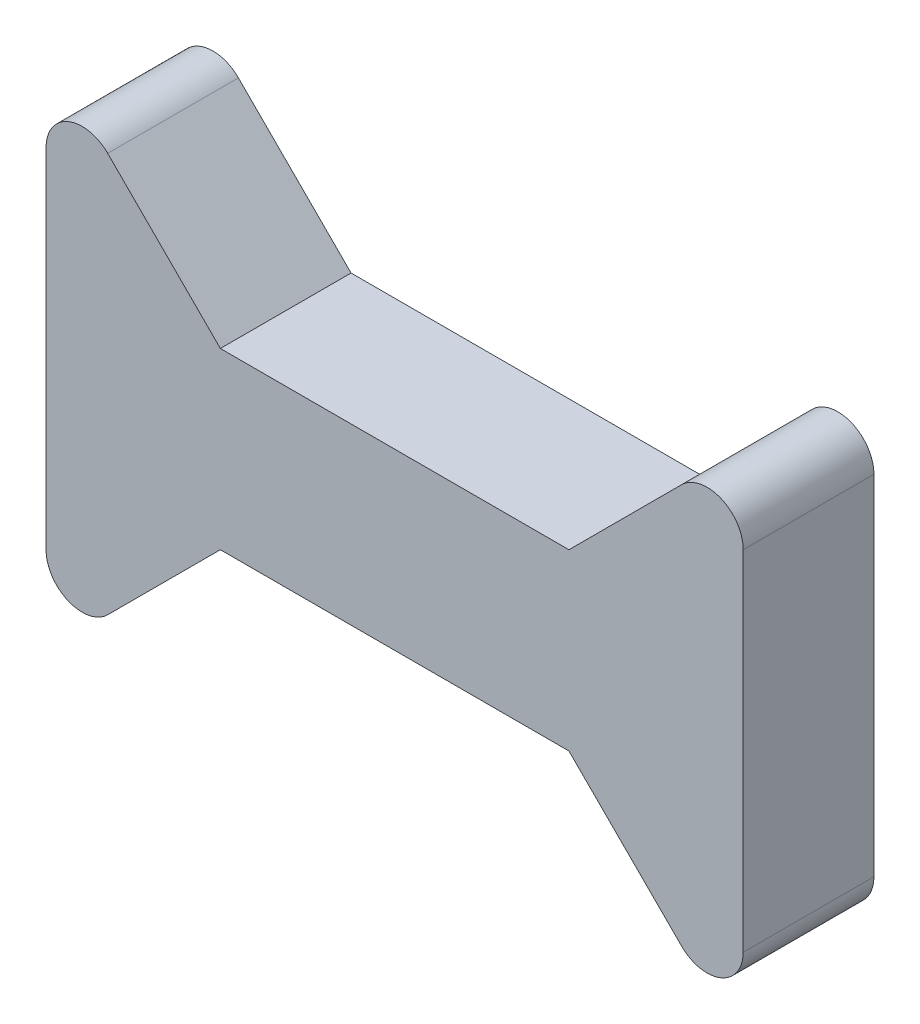
SolidWorks part; units mm, degrees
ref_plane "Front Plane" through (0, 0, 0) normal (0, 0, 1) x (1, 0, 0)
ref_plane "Top Plane" through (0, 0, 0) normal (0, 1, 0) x (1, 0, 0)
ref_plane "Right Plane" through (0, 0, 0) normal (1, 0, 0) x (0, 0, -1)
sketch "Sketch1" plane through (0, 0, 0) normal (0, 0, 1) x (1, 0, 0)
  line L0 (0, -5) -> (0, 5) construction
  line L1 (-20, 0) -> (20, 0) construction
  line L2 (-10, 5) -> (10, 5)
  line L3 (10, 5) -> (16.4645, 11.4645)
  line L4 (20, 10) -> (20, -10)
  line L5 (10, -5) -> (16.4645, -11.4645)
  line L6 (-10, -5) -> (10, -5)
  line L7 (-10, -5) -> (-16.4645, -11.4645)
  line L8 (-20, 10) -> (-20, -10)
  line L9 (-10, 5) -> (-16.4645, 11.4645)
  arc A0 (16.4645, 11.4645) -> (20, 10) centre (17.9289, 10) cw
  arc A1 (16.4645, -11.4645) -> (20, -10) centre (17.9289, -10) ccw
  arc A2 (-16.4645, -11.4645) -> (-20, -10) centre (-17.9289, -10) cw
  arc A3 (-16.4645, 11.4645) -> (-20, 10) centre (-17.9289, 10) ccw
  point P4 (0, 0)
  point P8 (0, 0)
  point P12 (50.942, 0)
  dimension "D1" = 135
  dimension "D2" = 10
  dimension "D3" = 20
  dimension "D4" = 20
  dimension "D5" = 10
extrude "Boss-Extrude1" add sketch "Sketch1" along normal blind 7.5
